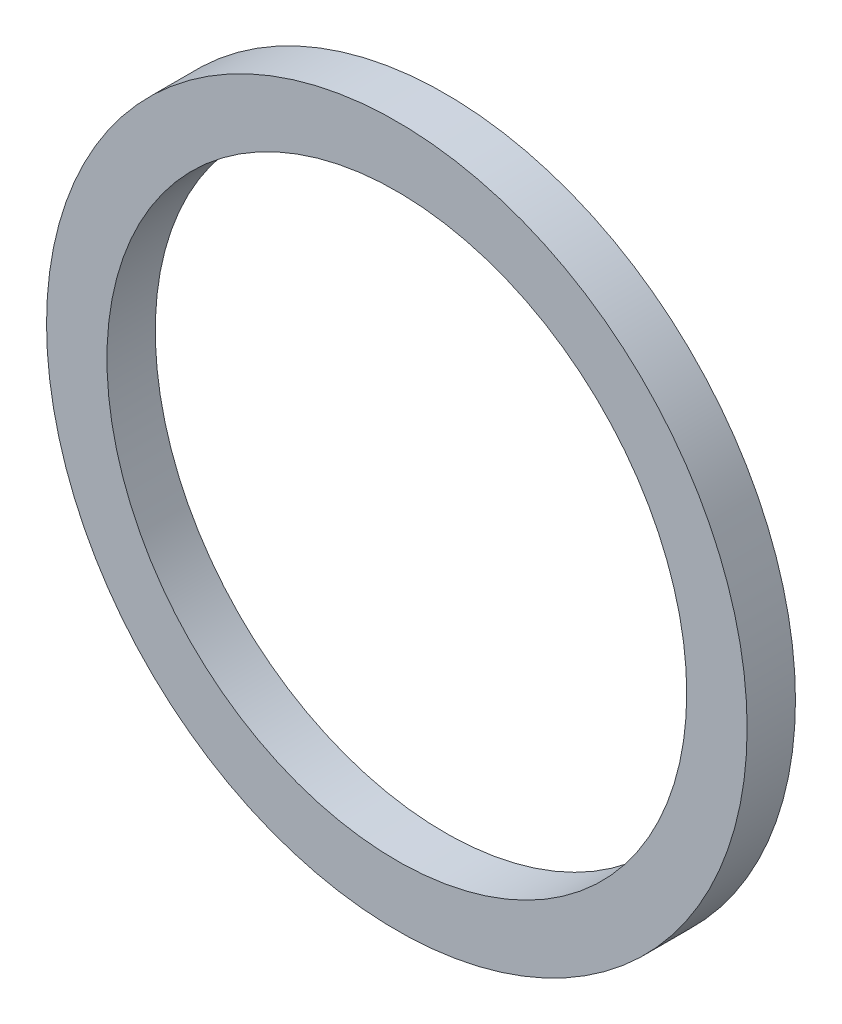
SolidWorks part; units mm, degrees
ref_plane "Front Plane" through (0, 0, 0) normal (0, 0, 1) x (1, 0, 0)
ref_plane "Top Plane" through (0, 0, 0) normal (0, 1, 0) x (1, 0, 0)
ref_plane "Right Plane" through (0, 0, 0) normal (1, 0, 0) x (0, 0, -1)
sketch "Sketch1" plane through (0, 0, 0) normal (0, 0, 1) x (1, 0, 0)
  circle A0 centre (0, 0) radius 72.5
  circle A1 centre (0, 0) radius 60
  dimension "D1" = 145
  dimension "D2" = 120
extrude "Boss-Extrude1" add sketch "Sketch1" along normal blind 10
equation "\"smallPulleyTeeth\"= 30"
equation "\"largePulleyTeeth\"= 30"
equation "\"eighthThick\"= 2.9mm"
equation "\"sixteenthThick\" = 1.7mm"
equation "\"quarterThick\"=5.9mm"
equation "\"OD\" = 145mm"
equation "\"puckAngle\" = 60.5deg"
equation "\"puckDiam\" = 76.5mm"
equation "\"axlePress\" = 5.9mm"
equation "\"press\" = 0.2mm"
equation "\"wheelClear\" = 0.3mm"
equation "\"10-32clear\" = 4.5mm"
equation "\"6-32clear\" = 3.3mm"
equation "\"8-32clear\" = 4.0mm"
equation "\"wheelHeight\" = 21mm"
equation "\"wheelWell\" = 62mm"
equation "\"D1@Sketch1\"=\"OD\""
